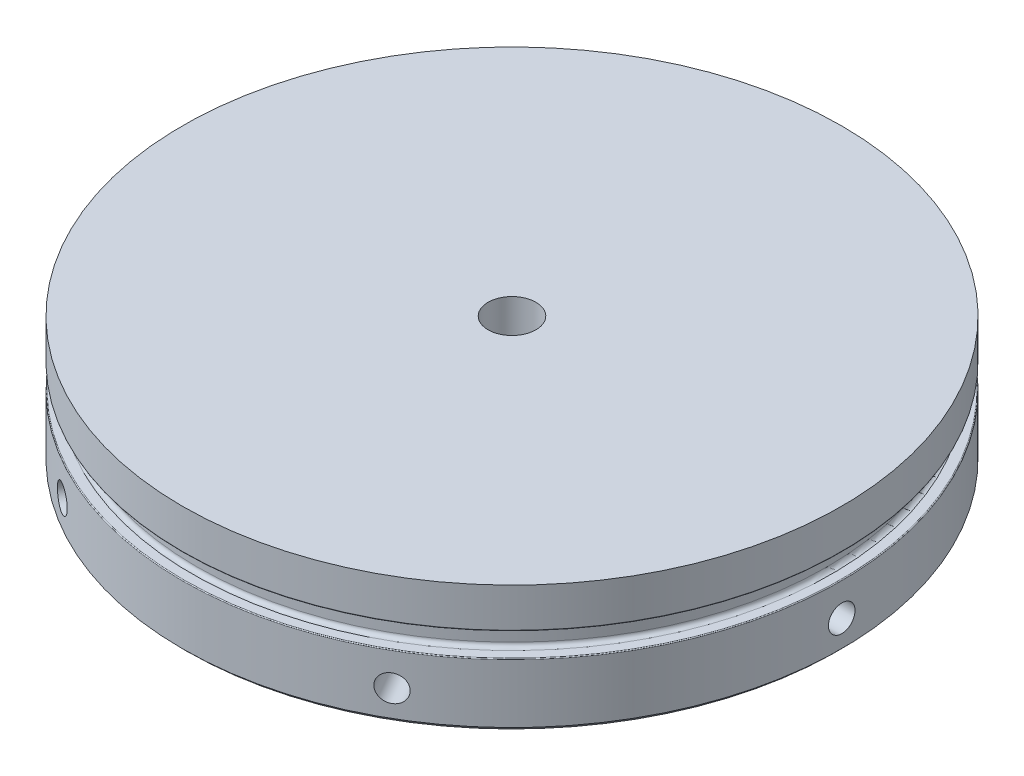
SolidWorks part; units mm, degrees
ref_plane "Front Plane" through (0, 0, 0) normal (0, 0, 1) x (1, 0, 0)
ref_plane "Top Plane" through (0, 0, 0) normal (0, 1, 0) x (1, 0, 0)
ref_plane "Right Plane" through (0, 0, 0) normal (1, 0, 0) x (0, 0, -1)
sketch "Sketch1" plane through (0, 0, 0) normal (0, 0, 1) x (1, 0, 0)
  line L0 (0, 0) -> (0, 32183.2735) construction
  line L1 (0, 0) -> (0, 38.1)
  line L2 (0, 38.1) -> (-98.3869, 38.1)
  line L3 (-98.3869, 38.1) -> (-98.3869, 26.1874)
  line L4 (-98.3869, 26.1874) -> (-94.107, 26.1874)
  line L5 (-94.107, 26.1874) -> (-94.107, 19.05)
  line L6 (-94.107, 19.05) -> (-98.3869, 19.05)
  line L7 (-98.3869, 19.05) -> (-98.3869, 6.5512)
  line L9 (-98.3869, 6.5512) -> (-98.3869, 0)
  line L10 (-98.3869, 0) -> (0, 0)
  dimension "D3" = 188.214
  dimension "D4" = 196.7738
  dimension "D5" = 7.1374
  dimension "D6" = 38.1
  dimension "D7" = 19.05
revolve "Revolve1" add sketch "Sketch1" angle 360 about L0
fillet "Fillet1" radius 1.27 2 edges at (0, 26.1874, -94.107) (0, 19.05, -94.107)
fillet "Fillet2" radius 0.254 2 edges at (0, 19.05, -98.3869) (0, 26.1874, -98.3869)
chamfer "Chamfer1" distance 1.27 angle 45 1 edges at (0, 0, -98.3869)
hole_wizard "3/8 NPT Tapped Hole3" positions "Sketch6" profile "Sketch7" size "3/8" standard "ANSI Inch" end condition through all
sketch "Sketch6" plane through (0, 0, 0) normal (0, -1, 0) x (1, 0, 0)
  point P0 (0, 0)
sketch "Sketch7" plane through (0, 0, 0) normal (1, 0, 0) x (0, 0, -1)
  line L0 (0, 0) -> (0, 38.1)
  line L1 (0, 38.1) -> (7.1374, 38.1)
  line L2 (-8.25, 10.3378) -> (-8.5727, 0) construction
  line L3 (7.1374, 38.1) -> (7.1374, 10.3378)
  line L4 (7.1374, 10.3378) -> (8.25, 10.3378)
  line L5 (8.25, 10.3378) -> (8.5727, 0)
  line L7 (8.5727, 0) -> (0, 0)
  line L8 (0, -6.35) -> (0, 107.95) construction
  line L11 (-7.1374, 10.3378) -> (-8.25, 10.3378) construction
  dimension "Thru Tap Drill Dia." = 14.2748
  dimension "Thru Tap Drill Depth" = 38.1
  dimension "Thread Dia." = 17.1455
  dimension "Thread Angle" = 3.576
  dimension "Thread Depth" = 10.3378
hole_wizard "3/8-16 Tapped Hole2" positions "3DSketch3" profile "Sketch9" tap size "3/8-16" standard "ANSI Inch"
sketch3d "3DSketch3"
  point P0 (-98.3868, 9.1058, 0.1228)
sketch "Sketch9" plane through (-98.3868, 9.1058, 0.1228) normal (0, 1, 0) x (0.0012, 0, 1)
  line L0 (0, 0) -> (0, 37.9447)
  line L1 (0, 37.9447) -> (3.9687, 35.56)
  line L2 (3.9687, 35.56) -> (3.9687, 0)
  line L5 (3.9687, 0) -> (0, 0)
  line L10 (0, 37.9447) -> (-3.9688, 35.56) construction
  line L11 (0, -6.35) -> (0, 107.95) construction
  dimension "Tap Drill Dia." = 7.9375
  dimension "Tap Drill Depth" = 35.56
  dimension "Drill Angle" = 118
cosmetic thread "Hole Thread4" parameters "D1"=10.3378, "D2"=9.525
pattern_circular "CirPattern1" count 6 over 360 about axis through (0, 0, 0) along (0, -1, 0) of "3/8-16 Tapped Hole2" reverse direction yes
cosmetic thread "Hole Thread5" parameters "D1"=10.3378, "D2"=9.525
cosmetic thread "Hole Thread6" parameters "D1"=10.3378, "D2"=9.525
cosmetic thread "Hole Thread7" parameters "D1"=10.3378, "D2"=9.525
cosmetic thread "Hole Thread8" parameters "D1"=10.3378, "D2"=9.525
cosmetic thread "Hole Thread9" parameters "D1"=10.3378, "D2"=9.525
